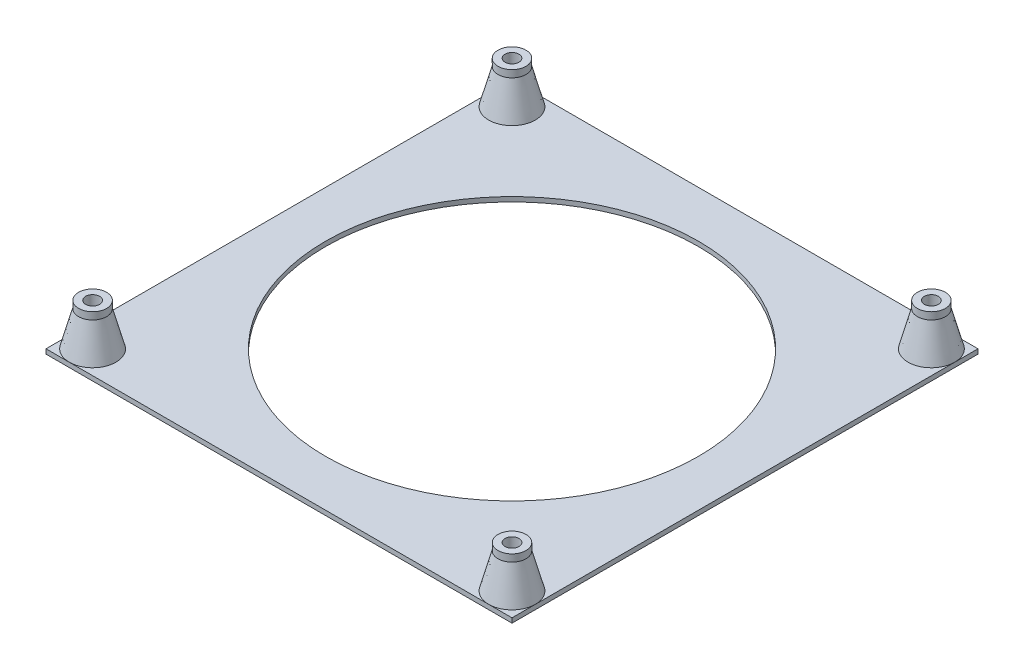
SolidWorks part; units mm, degrees
ref_plane "Front Plane" through (0, 0, 0) normal (0, 0, 1) x (1, 0, 0)
ref_plane "Top Plane" through (0, 0, 0) normal (0, 1, 0) x (1, 0, 0)
ref_plane "Right Plane" through (0, 0, 0) normal (1, 0, 0) x (0, 0, -1)
sketch "Sketch1" plane through (0, 0, 0) normal (0, 1, 0) x (1, 0, 0)
  line L0 (-89.4, 20.5) -> (-64.5371, 20.5) construction
  line L1 (50, -50) -> (-50, -50)
  line L2 (50, -50) -> (50, 50)
  line L3 (50, 50) -> (-50, 50)
  line L4 (-50, -50) -> (-50, 50)
  line L5 (50, -50) -> (-50, 50) construction
  line L6 (50, 50) -> (-50, -50) construction
  line L7 (77.6, -58.5) -> (-89.4, -58.5) construction
  line L8 (77.6, -58.5) -> (77.6, 58.5) construction
  line L9 (77.6, 58.5) -> (-89.4, 58.5) construction
  line L10 (-89.4, -58.5) -> (-89.4, 58.5) construction
  line L11 (77.6, -58.5) -> (-89.4, 58.5) construction
  line L12 (77.6, 58.5) -> (-89.4, -58.5) construction
  line L13 (-55, 24.5) -> (-89.4, 24.5) construction
  line L14 (-55, 24.5) -> (-55, 48.5) construction
  line L15 (-55, 48.5) -> (-89.4, 48.5) construction
  line L16 (-89.4, 24.5) -> (-89.4, 48.5) construction
  line L17 (-55, 24.5) -> (-89.4, 48.5) construction
  line L18 (-55, 48.5) -> (-89.4, 24.5) construction
  line L19 (-55, -7.5) -> (-89.4, 16.5) construction
  line L20 (-55, 16.5) -> (-89.4, -7.5) construction
  line L21 (-89.4, 16.5) -> (-89.4, -7.5) construction
  line L22 (-55, -7.5) -> (-89.4, -7.5) construction
  line L23 (-55, 16.5) -> (-55, -7.5) construction
  line L24 (-55, 16.5) -> (-89.4, 16.5) construction
  line L26 (-140.7168, 29.2348) -> (-113.7168, 29.2348) construction
  line L27 (-140.7168, 29.2348) -> (-140.7168, -19.7652) construction
  line L28 (-140.7168, -19.7652) -> (-113.7168, -19.7652) construction
  line L29 (-113.7168, 29.2348) -> (-113.7168, -19.7652) construction
  line L30 (-140.7168, 29.2348) -> (-113.7168, -19.7652) construction
  line L31 (-140.7168, -19.7652) -> (-113.7168, 29.2348) construction
  circle A0 centre (0, 0) radius 40
  point P0 (0, 0)
  point P6 (-5.9, 0)
  point P12 (-72.2, 36.5)
  point P22 (-72.2, 4.5)
  point P23 (-127.2168, 4.7348)
  dimension "D13" = 80
  dimension "D1" = 100
  dimension "D2" = 100
  dimension "D3" = 167
  dimension "D4" = 117
  dimension "D5" = 34.4
  dimension "D6" = 5
  dimension "D7" = 24
  dimension "D8" = 27.6
  dimension "D9" = 4
  dimension "D10" = 27
  dimension "D11" = 49
  dimension "D12" = 10
extrude "Boss-Extrude1" add sketch "Sketch1" along normal blind 1
sketch "Sketch2" plane through (0, 1, 0) normal (0, 1, 0) x (1, 0, 0)
  line L0 (-50, -50) -> (50, -50) construction
  line L1 (-50, 50) -> (-50, -50) construction
  circle A0 centre (-45, -45) radius 3
  circle A1 centre (-45, -45) radius 1.5
  dimension "D3" = 6
  dimension "D4" = 3
  dimension "D1" = 5
  dimension "D2" = 5
extrude "Boss-Extrude2" add sketch "Sketch2" along normal blind 9 contours A1 | A0 A1 region at (-47.9151, 1, 45) region at (-45, 1, 45)
extrude "Cut-Extrude1" cut sketch "Sketch2<3>" against normal blind 10 from surface contours A1 region at (-45, 1, 45) starting at face at (-45, 10, 48)
sketch "Sketch2<3>" plane through (0, 1, 0) normal (0, 1, 0) x (1, 0, 0) same geometry as "Sketch2"
mirror "Mirror1" about plane through (0, 0, 0) normal (1, 0, 0) of "Cut-Extrude1", "Boss-Extrude2"
mirror "Mirror2" about plane through (0, 0, 0) normal (0, 0, 1) of "Mirror1"
chamfer "Chamfer1" distance 2 angle 75 4 edges at (-45, 1, 48) (45, 1, 48) (45, 1, -48) (-45, 1, -42) first distance on face at (-45, 1, -42)
